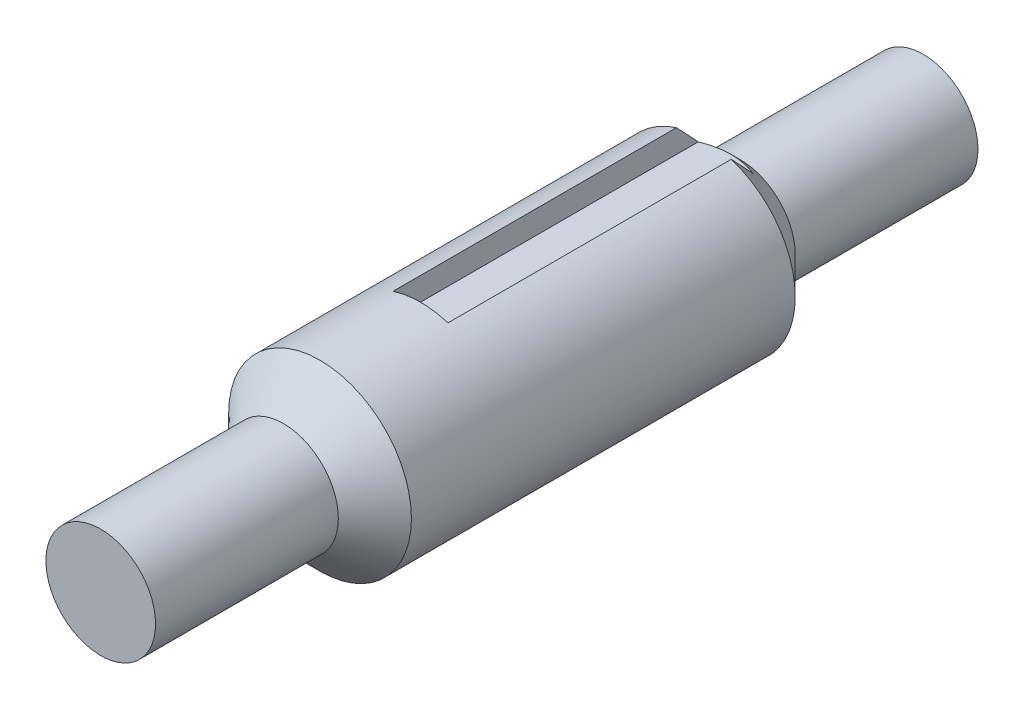
SolidWorks part; units mm, degrees
ref_plane "Front Plane" through (0, 0, 0) normal (0, 0, 1) x (1, 0, 0)
ref_plane "Top Plane" through (0, 0, 0) normal (0, 1, 0) x (1, 0, 0)
ref_plane "Right Plane" through (0, 0, 0) normal (1, 0, 0) x (0, 0, -1)
sketch "Sketch2" plane through (0, 0, 0) normal (0, 0, 1) x (1, 0, 0)
  circle A0 centre (0, 0) radius 10
  circle A1 centre (0, 0) radius 22.5
  dimension "D1" = 20
  dimension "D2" = 45
extrude "Boss-Extrude1" add sketch "Sketch2" along normal blind 30 contours A0 region at (0, 0, 0)
sketch "Sketch5" plane through (0, 0, 0) normal (0, 0, 1) x (1, 0, 0)
  circle A0 centre (0, 0) radius 6
  dimension "D1" = 12
extrude "Boss-Extrude3" add sketch "Sketch5" against normal blind 30
sketch "Sketch3" plane through (0, 0, 0) normal (0, 0, 1) x (1, 0, 0)
  line L0 (0, 0) -> (0, 20) construction
  line L2 (-3, 7) -> (3, 7)
  line L3 (-3, 7) -> (-3, 13)
  line L4 (-3, 13) -> (3, 13)
  line L5 (3, 7) -> (3, 13)
  line L6 (-3, 7) -> (3, 13) construction
  line L7 (-3, 13) -> (3, 7) construction
  circle A1 centre (0, 0) radius 10 construction
  point P3 (0, 10)
  point P8 (0, 0)
  dimension "D1" = 6
  dimension "D2" = 6
chamfer "Chamfer2" distance 10 angle 45 1 edges at (6, 0, 0)
extrude "Cut-Extrude1" cut sketch "Sketch3" along normal blind 25 and the other way through all
extrude "Boss-Extrude4" add sketch "Sketch5<3>" along normal blind 30 from surface starting at face at (10, 0, 30)
sketch "Sketch5<3>" plane through (0, 0, 0) normal (0, 0, 1) x (1, 0, 0) same geometry as "Sketch5"
chamfer "Chamfer3" distance 10 angle 45 1 edges at (6, 0, 30)
